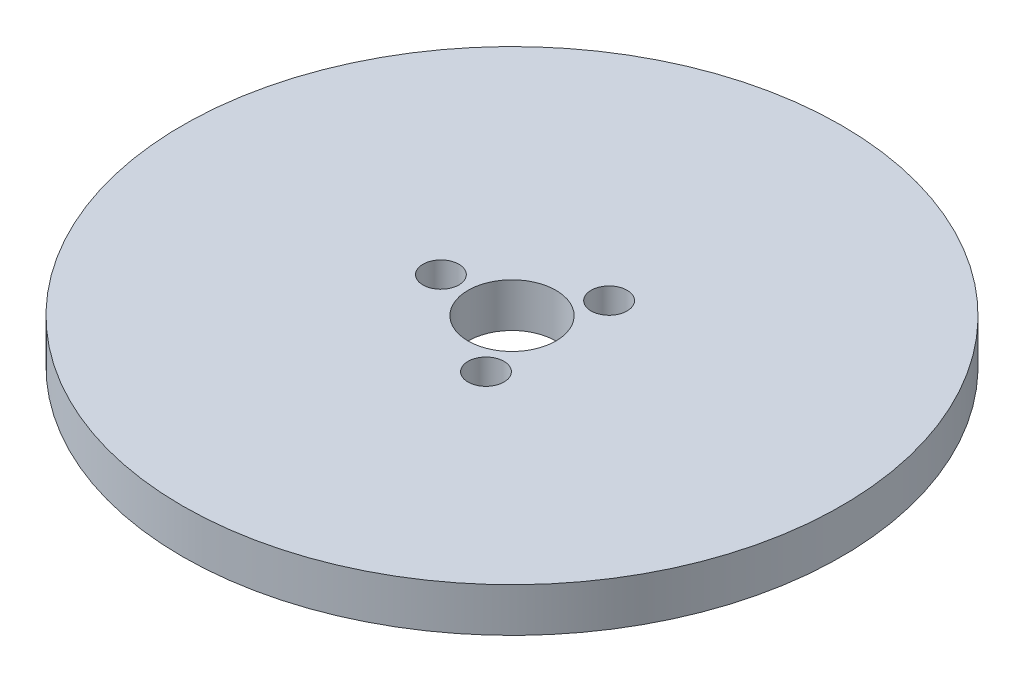
SolidWorks part; units mm, degrees
ref_plane "Front Plane" through (0, 0, 0) normal (0, 0, 1) x (1, 0, 0)
ref_plane "Top Plane" through (0, 0, 0) normal (0, 1, 0) x (1, 0, 0)
ref_plane "Right Plane" through (0, 0, 0) normal (1, 0, 0) x (0, 0, -1)
sketch "Sketch1" plane through (0, 0, 0) normal (0, 1, 0) x (1, 0, 0)
  circle A0 centre (0, 0) radius 75
  dimension "FLANGE_OD" = 150
extrude "Boss-Extrude1" add sketch "Sketch1" along normal blind 10
sketch "Sketch2" plane through (0, 0, 0) normal (0, 1, 0) x (1, 0, 0)
  circle A0 centre (0, 0) radius 10
  dimension "BORE_D" = 20
extrude "Cut-Extrude1" cut sketch "Sketch2" along normal through all
sketch "Sketch3" plane through (0, 10, 0) normal (0, 1, 0) x (1, 0, 0)
  circle A0 centre (0, 0) radius 16.177 construction
  circle A1 centre (-16.177, 0) radius 4.0938
  dimension "BOLT_D" = 8.1876
  dimension "BOLT_PCD" = 32.3541
extrude "Cut-Extrude2" cut sketch "Sketch3" against normal blind 6.0414
pattern_circular "CirPattern1" count 3 over 360 about axis through (0, 0, 0) along (0, 1, 0) of "Cut-Extrude2"
